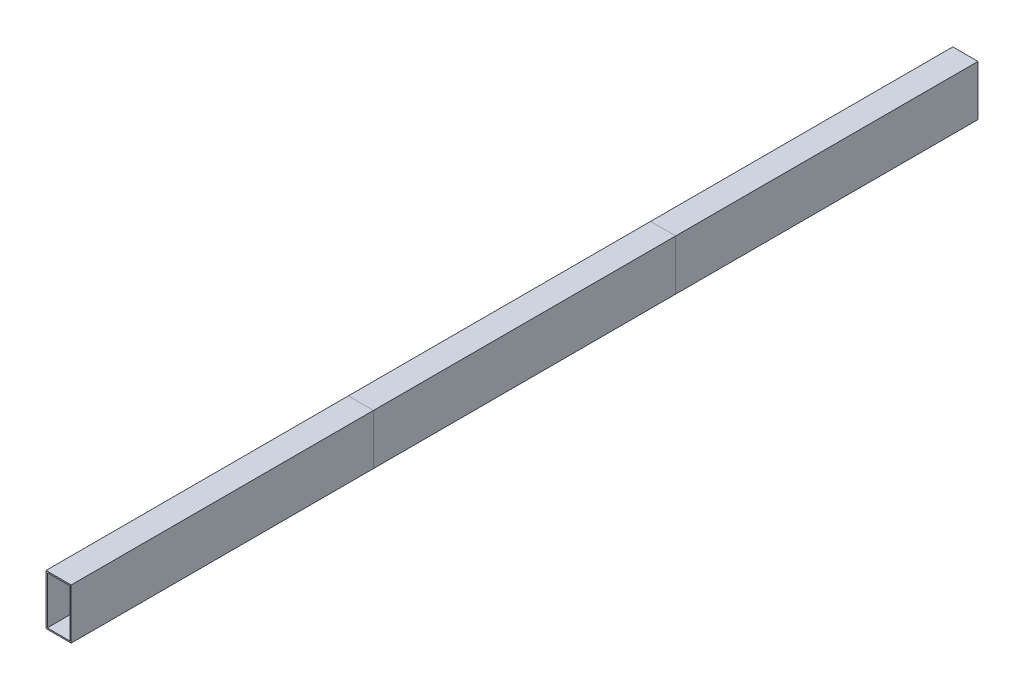
SolidWorks part; units mm, degrees
ref_plane "Спереди" through (0, 0, 0) normal (0, 0, 1) x (1, 0, 0)
ref_plane "Сверху" through (0, 0, 0) normal (0, 1, 0) x (1, 0, 0)
ref_plane "Справа" through (0, 0, 0) normal (1, 0, 0) x (0, 0, -1)
sketch "Эскиз1" plane through (0, 0, 0) normal (0, 0, 1) x (1, 0, 0)
  line L1 (-50, -100) -> (50, -100)
  line L2 (-50, -100) -> (-50, 100)
  line L3 (-50, 100) -> (50, 100)
  line L4 (50, -100) -> (50, 100)
  line L5 (-50, -100) -> (50, 100) construction
  line L6 (-50, 100) -> (50, -100) construction
  line L7 (-45, -95) -> (45, -95)
  line L8 (-45, -95) -> (-45, 95)
  line L9 (-45, 95) -> (45, 95)
  line L10 (45, -95) -> (45, 95)
  line L11 (-45, -95) -> (45, 95) construction
  line L12 (-45, 95) -> (45, -95) construction
  point P0 (0, 0)
  point P6 (0, 0)
  dimension "D1" = 100
  dimension "D2" = 200
  dimension "D3" = 90
  dimension "D4" = 190
extrude "Бобышка-Вытянуть1" add sketch "Эскиз1" along normal blind 1200
extrude "Бобышка-Вытянуть2" add sketch "Эскиз1<2>" along normal blind 1200 from surface separate body starting at face at (0, 0, 1200)
sketch "Эскиз1<2>" plane through (0, 0, 0) normal (0, 0, 1) x (1, 0, 0) same geometry as "Эскиз1"
extrude "Бобышка-Вытянуть3" add sketch "Эскиз1<3>" along normal blind 1200 from surface separate body starting at face at (0, 0, 2400)
sketch "Эскиз1<3>" plane through (0, 0, 0) normal (0, 0, 1) x (1, 0, 0) same geometry as "Эскиз1"
ref_point "Точка1"
ref_point "Точка2"
